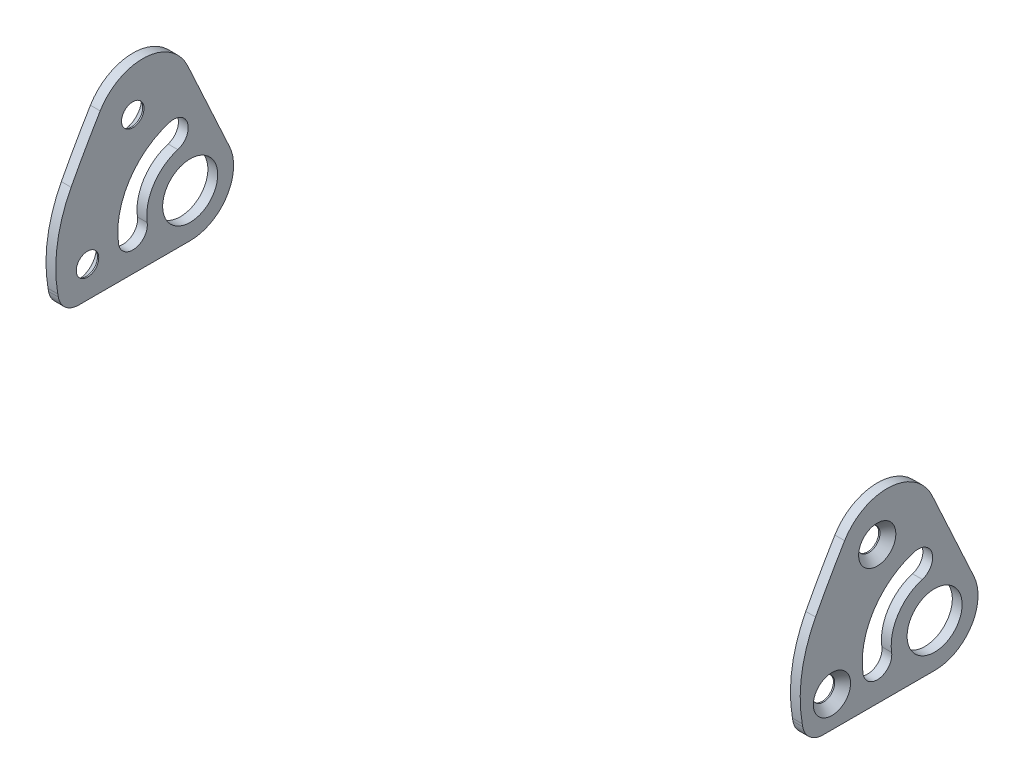
SolidWorks part; units mm, degrees
material "Ti-6Al-4VSolution treated and aged (SS)"
ref_plane "Front Plane" through (0, 0, 0) normal (0, 0, 1) x (1, 0, 0)
ref_plane "Top Plane" through (0, 0, 0) normal (0, 1, 0) x (1, 0, 0)
ref_plane "Right Plane" through (0, 0, 0) normal (1, 0, 0) x (0, 0, -1)
sketch "Sketch1" plane through (56.4, 0, 0) normal (1, 0, 0) x (0, 0, -1)
  line L1 (-167.5543, 20.32) -> (-158.5173, 20.32) construction
  line L2 (-175.7159, 20.32) -> (-155.9, 20.32)
  line L4 (-175.7159, 20.32) -> (-176.2234, 23.4009)
  line L6 (-149.8425, 29.7735) -> (-161.9603, 56.1208)
  arc A1 (-174.1784, 36.5691) -> (-161.9603, 56.1208) centre (-39.1995, -34.1873) cw
  circle A2 centre (-155.9, 26.9875) radius 4.2228
  arc A4 (-142.7292, 77.6491) -> (-174.1784, 36.5691) centre (-39.1995, -34.1873) ccw construction
  arc A6 (-176.22, -24.13) -> (-176.2234, 23.4009) centre (-310.9451, -0.3743) ccw construction
  arc A7 (-155.9, 20.32) -> (-149.8425, 29.7735) centre (-155.9, 26.9875) ccw
  arc A9 (-174.1784, 36.5691) -> (-176.2234, 23.4009) centre (-155.9, 26.9875) ccw construction
  arc A10 (-174.1784, 36.5691) -> (-176.2234, 23.4009) centre (-155.9, 26.9875) ccw
  arc A11 (-158.5857, 52.6676) -> (-156.0025, 47.6247) centre (-156.0183, 50.7997) ccw construction
  arc A12 (-156.2684, 43.745) -> (-169.7171, 44.4951) centre (-163.1912, 40.561) ccw
  arc M26 (-176.2234, 23.4009) -> (-176.22, -24.13) centre (-310.9451, -0.3743) cw
  arc M38 (-174.1784, 36.5691) -> (-176.2234, 23.4009) centre (-155.9, 26.9875) ccw
  circle M87 centre (-163.0439, 43.0343) radius 1.0922
  circle M88 centre (-171.6603, 25.0825) radius 1.0922
  dimension "D1" = 8.4455
  dimension "D2" = 7.62
extrude "Boss-Extrude1" add sketch "Sketch1" along normal blind 1.5 contours L6 A12 A1 L2 A7 A2 M38 M26 M88 M87 | M87 | M88 region at (56.4, 32.6978, 164.0908) region at (56.4, 43.0343, 163.0439) region at (56.4, 25.0825, 171.6603)
sketch "Sketch2" plane through (57.9, 0, 0) normal (1, 0, 0) x (0, 0, -1)
  line L4 (-161.5796, 23.495) -> (-166.5679, 23.495) construction
  line L6 (-155.5123, 34.5029) -> (-158.2442, 40.4426) construction
  line L9 (-149.8425, 29.7735) -> (-156.2684, 43.745) construction
  line L10 (-175.7159, 20.32) -> (-155.9, 20.32) construction
  arc A9 (-155.9, 20.32) -> (-149.8425, 29.7735) centre (-155.9, 26.9875) ccw construction
  arc A10 (-174.1784, 36.5691) -> (-176.2234, 23.4009) centre (-155.9, 26.9875) ccw construction
  arc A12 (-157.7921, 33.3809) -> (-162.4991, 26.035) centre (-155.9, 26.9875) ccw
  arc A16 (-159.0535, 37.6432) -> (-166.8985, 25.4) centre (-155.9, 26.9875) ccw
  arc A18 (-157.7921, 33.3809) -> (-159.0535, 37.6432) centre (-158.4228, 35.512) ccw
  arc A19 (-162.4991, 26.035) -> (-166.8985, 25.4) centre (-164.6988, 25.7175) cw
  dimension "D1" = 3.175
  dimension "D2" = 3.175
  dimension "D3" = 9.525
extrude "Cut-Extrude1" cut sketch "Sketch2" against normal up to next and the other way through all contours L6 A16 L4 A12 region at (57.9, 31.2206, 162.5063)
fillet "Fillet3" radius 3.175 1 edges at (57.15, 20.32, 175.7159)
sketch "Sketch3" plane through (57.9, 0, 0) normal (1, 0, 0) x (0, 0, -1)
  line L2 (-173.0168, 20.32) -> (-155.9, 20.32) construction
  circle A0 centre (-171.6603, 25.0825) radius 4.7625 construction
  circle A1 centre (-164.7108, 41.4771) radius 5.8456 construction
  arc A2 (-169.7171, 44.4951) -> (-174.1784, 36.5691) centre (-39.1995, -34.1873) ccw construction
  arc A3 (-159.0535, 37.6432) -> (-166.8985, 25.4) centre (-155.9, 26.9875) ccw construction
  arc A4 (-156.2684, 43.745) -> (-169.7171, 44.4951) centre (-163.1912, 40.561) ccw construction
  arc A5 (-174.1784, 36.5691) -> (-176.2234, 23.4009) centre (-155.9, 26.9875) ccw construction
hole_wizard "CSK for #4 Flat Head Machine Screw1" positions "Sketch4" profile "Sketch6" countersink size "#4" standard "ANSI Inch" end condition up to next
sketch "Sketch4" plane through (57.9, 0, 0) normal (1, 0, 0) x (0, 0, -1)
  point P0 (-171.6603, 25.0825)
  point P3 (-164.7108, 41.4771)
sketch "Sketch6" plane through (57.9, 25.0825, 171.6603) normal (0, 1, 0) x (0, 0, -1)
  line L0 (0, 0) -> (0, 1.5)
  line L1 (0, 1.5) -> (1.7272, 1.5)
  line L2 (1.7272, 1.5) -> (1.7272, 1.3003)
  line L3 (1.7272, 1.3003) -> (2.8575, 0)
  line L5 (2.8575, 0) -> (0, 0)
  line L6 (-1.7272, 1.3003) -> (-2.8575, 0) construction
  line L11 (0, -6.35) -> (0, 107.95) construction
  dimension "Thru Hole Dia." = 3.4544
  dimension "Thru Hole Depth" = 1.5
  dimension "Near C'Sink Dia." = 5.715
  dimension "Near C'Sink Angle" = 82
mirror "Mirror2" about plane through (0, 0, 0) normal (1, 0, 0) of bodies 110 101
equation "\"weapon shaft threads\"= 5 / 16"
equation "\"D1@Sketch1\"=\"weapon shaft threads\" + .02in"
equation "\"D1@Boss-Extrude1\"=1.5mm"
